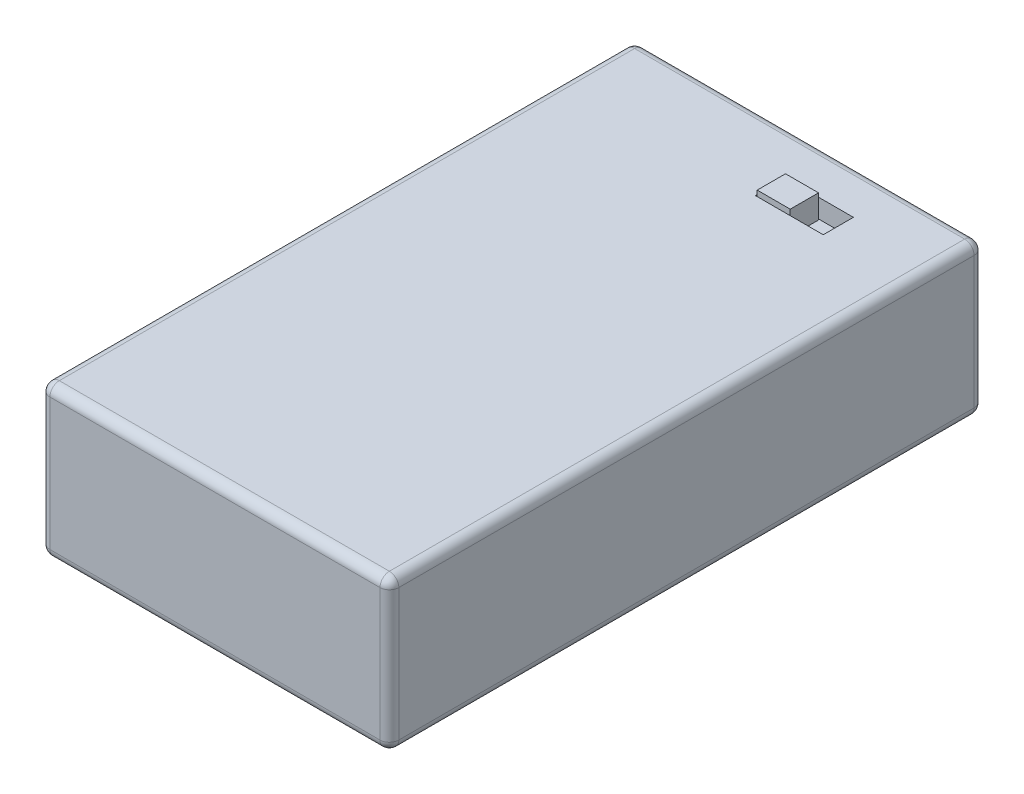
SolidWorks part; units mm, degrees
ref_plane "前视基准面" through (0, 0, 0) normal (0, 0, 1) x (1, 0, 0)
ref_plane "上视基准面" through (0, 0, 0) normal (0, 1, 0) x (1, 0, 0)
ref_plane "右视基准面" through (0, 0, 0) normal (1, 0, 0) x (0, 0, -1)
other "Configuration Table"
sketch "草图1" plane through (0, 0, 0) normal (0, 1, 0) x (1, 0, 0)
  line L1 (-18.5, -31.5) -> (18.5, -31.5)
  line L2 (-18.5, -31.5) -> (-18.5, 31.5)
  line L3 (-18.5, 31.5) -> (18.5, 31.5)
  line L4 (18.5, -31.5) -> (18.5, 31.5)
  line L5 (-18.5, -31.5) -> (18.5, 31.5) construction
  line L6 (-18.5, 31.5) -> (18.5, -31.5) construction
  line L19 (2.5, 26.5) -> (6, 26.5)
  line L20 (2.5, 26.5) -> (2.5, 23.5)
  line L29 (2.5, 23.5) -> (6, 23.5)
  line L30 (6, 26.5) -> (6, 23.5)
  line L31 (2.4, 26.6) -> (9.6, 26.6)
  line L32 (2.4, 26.6) -> (2.4, 23.4)
  line L33 (2.4, 23.4) -> (9.6, 23.4)
  line L34 (9.6, 26.6) -> (9.6, 23.4)
  point P0 (0, 0)
  point P14 (2.4, 25)
  point P15 (2.5, 25)
  dimension "D1" = 63
  dimension "D2" = 8
  dimension "D7" = 0.1
  dimension "D5" = 16
  dimension "D6" = 3.5
  dimension "D3" = 37
  dimension "D4" = 3
  dimension "D8" = 0.1
  dimension "D9" = 7.2
extrude "凸台-拉伸1" add sketch "草图1" along normal blind 16 contours L4 L3 L2 L1
fillet "圆角1" radius 1 12 edges at (18.5, 8, -31.5) (18.5, 8, 31.5) (-18.5, 8, -31.5) (-18.5, 8, 31.5) (0, 0, -31.5) (0, 16, -31.5) (0, 16, 31.5) (0, 0, 31.5) (18.5, 0, 0) (18.5, 16, 0) (-18.5, 0, 0) (-18.5, 16, 0)
extrude "切除-拉伸1" cut sketch "草图1<9>" against normal blind 2 from surface contours L31 L34 L33 L32 starting at face at (0, 16, 0)
sketch "草图1<9>" plane through (0, 0, 0) normal (0, 1, 0) x (1, 0, 0) same geometry as "草图1"
extrude "凸台-拉伸2" add sketch "草图1<10>" along normal blind 2.5 from surface contours L30 L29 L20 L19 starting at face at (6, 14, -25)
sketch "草图1<10>" plane through (0, 0, 0) normal (0, 1, 0) x (1, 0, 0) same geometry as "草图1"
sketch "草图2" plane through (0, 0, -31.5) normal (0, 0, -1) x (-1, 0, 0)
  line L0 (-17.5, 16) -> (17.5, 16) construction
  line L1 (18.5, 15) -> (18.5, 1) construction
  circle A0 centre (11.5, 11) radius 2.5
  point P2 (8.7275, 9.9301)
  dimension "D3" = 5
  dimension "D1" = 5
  dimension "D2" = 7
extrude "切除-拉伸2" cut sketch "草图2" against normal blind 2 contours A0
